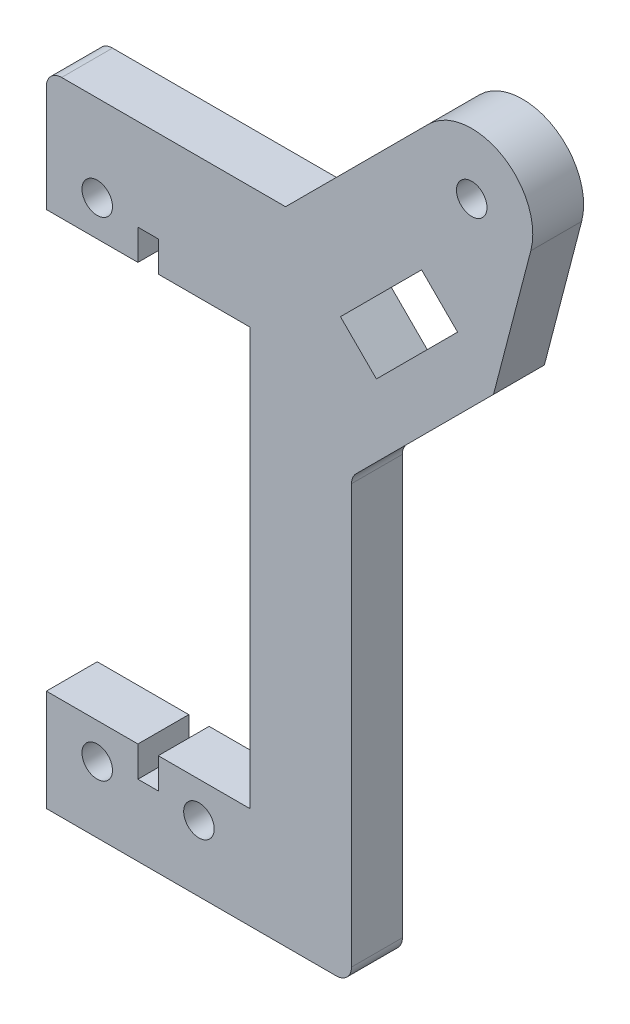
SolidWorks part; units mm, degrees
ref_plane "Plan de face" through (0, 0, 0) normal (0, 0, 1) x (1, 0, 0)
ref_plane "Plan de dessus" through (0, 0, 0) normal (0, 1, 0) x (1, 0, 0)
ref_plane "Plan de droite" through (0, 0, 0) normal (1, 0, 0) x (0, 0, -1)
sketch "Esquisse1" plane through (0, 0, 0) normal (0, 0, 1) x (1, 0, 0)
  line L0 (0, 10) -> (0, 0)
  line L1 (0, 0) -> (30, 0)
  line L2 (10, 10) -> (10, 51) construction
  line L3 (0, 63) -> (23.5147, 63)
  line L4 (36.8905, 64.3141) -> (28.9121, 56.3358)
  line L5 (9, 51) -> (0, 51)
  line L6 (36.8905, 64.3141) -> (40.426, 60.7786)
  line L7 (20, 10) -> (11, 10)
  line L8 (0, 30.5) -> (0, 10)
  line L9 (0, 30.5) -> (20, 30.5) construction
  line L10 (20, 10) -> (20, 51)
  line L11 (20, 51) -> (11, 51)
  line L12 (47.626, 71.307) -> (43.9615, 57.2431)
  line L13 (43.9615, 57.2431) -> (30, 43.2815)
  line L14 (28.9121, 56.3358) -> (32.4476, 52.8002)
  line L15 (32.4476, 52.8002) -> (40.426, 60.7786)
  line L16 (37.5772, 77.0624) -> (23.5147, 63)
  line L17 (11, 10) -> (11, 7)
  line L18 (9, 10) -> (0, 10)
  line L19 (9, 51) -> (9, 54)
  line L20 (9, 54) -> (11, 54)
  line L21 (11, 51) -> (11, 54)
  line L22 (9, 7) -> (11, 7)
  line L23 (9, 10) -> (9, 7)
  line L24 (30, 43.2815) -> (30, 0)
  line L25 (0, 63) -> (0, 51)
  line L26 (40.426, 60.7786) -> (43.9615, 57.2431) construction
  circle A0 centre (5, 54.5) radius 1.5
  circle A1 centre (15, 54.5) radius 1.5 construction
  circle A2 centre (15, 6.5) radius 1.5
  circle A3 centre (5, 6.5) radius 1.5
  circle A4 centre (41.8198, 72.8198) radius 1.5
  circle A5 centre (41.8198, 72.8198) radius 1.725 construction
  arc A6 (37.5772, 77.0624) -> (47.626, 71.307) centre (41.8198, 72.8198) cw
  dimension "D6" = 20
  dimension "D8" = 5
  dimension "D11" = 3
  dimension "D16" = 10
  dimension "D5" = 3
  dimension "D12" = 11.2831
  dimension "D13" = 6
  dimension "D1" = 41
  dimension "D2" = 12
  dimension "D3" = 3.5
  dimension "D4" = 5
  dimension "D7" = 5
  dimension "D9" = 2
  dimension "D10" = 3
  dimension "D14" = 10
extrude "Boss.-Extru.1" add sketch "Esquisse1" along normal blind 5 contours L3 L25 L1 L4 L14 L15 L23 L18 L8 L5 L19 L20 L21 L11 L10 L7 L17 L22 A0 A2 A3 region at (23.9049, 40.6848, 0)
fillet "Congé3" radius 1.5 3 edges at (0, 63, 2.5) (30, 0, 2.5) (30, 43.2815, 2.5)
